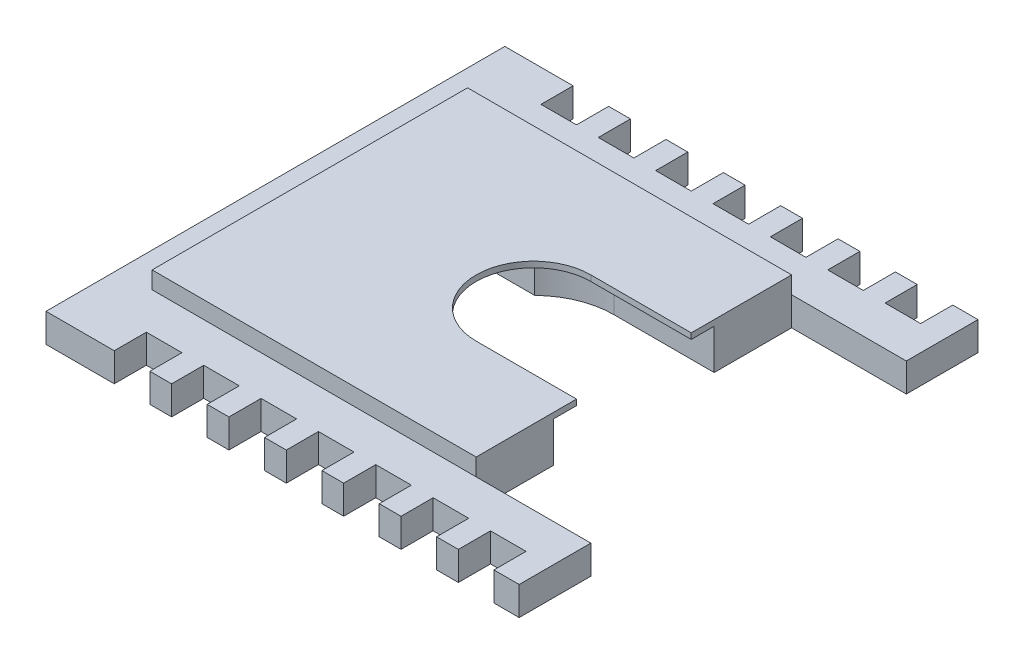
SolidWorks part; units mm, degrees
ref_plane "Front Plane" through (0, 0, 0) normal (0, 0, 1) x (1, 0, 0)
ref_plane "Top Plane" through (0, 0, 0) normal (0, 1, 0) x (1, 0, 0)
ref_plane "Right Plane" through (0, 0, 0) normal (1, 0, 0) x (0, 0, -1)
sketch "Sketch1" plane through (0, 0, 0) normal (0, 1, 0) x (1, 0, 0)
  line L0 (0, -50.8) -> (0, 50.8)
  line L16 (79.375, 34.925) -> (79.375, -34.925)
  line L17 (0, 0) -> (12.404, 0) construction
  line L18 (117.475, 34.925) -> (117.475, 0) construction
  line L19 (104.775, 50.8) -> (104.775, 34.925)
  line L20 (104.775, -34.925) -> (79.375, -34.925)
  line L21 (104.775, -50.8) -> (104.775, -34.925)
  line L22 (98.425, -50.8) -> (104.775, -50.8)
  line L23 (98.425, -44.45) -> (98.425, -50.8)
  line L24 (92.075, -44.45) -> (98.425, -44.45)
  line L25 (92.075, -50.8) -> (92.075, -44.45)
  line L26 (85.725, -50.8) -> (92.075, -50.8)
  line L27 (85.725, -44.45) -> (85.725, -50.8)
  line L29 (28.575, -50.8) -> (28.575, -44.45)
  line L30 (22.225, -50.8) -> (28.575, -50.8)
  line L31 (22.225, -44.45) -> (22.225, -50.8)
  line L32 (15.875, -44.45) -> (22.225, -44.45)
  line L33 (15.875, -50.8) -> (15.875, -44.45)
  line L34 (0, -50.8) -> (15.875, -50.8)
  line L35 (28.575, -44.45) -> (34.925, -44.45)
  line L36 (34.925, -44.45) -> (34.925, -50.8)
  line L37 (34.925, -50.8) -> (41.275, -50.8)
  line L38 (41.275, -50.8) -> (41.275, -44.45)
  line L39 (41.275, -44.45) -> (47.625, -44.45)
  line L40 (79.375, -44.45) -> (79.375, -50.8)
  line L41 (79.375, -50.8) -> (73.025, -50.8)
  line L42 (73.025, -50.8) -> (73.025, -44.45)
  line L43 (79.375, -44.45) -> (85.725, -44.45)
  line L44 (47.625, -44.45) -> (47.625, -50.8)
  line L45 (47.625, -50.8) -> (66.675, -50.8)
  line L46 (66.675, -50.8) -> (66.675, -44.45)
  line L47 (66.675, -44.45) -> (73.025, -44.45)
  line L48 (0, 50.8) -> (15.875, 50.8)
  line L49 (104.775, 34.925) -> (79.375, 34.925)
  line L50 (66.675, 44.45) -> (73.025, 44.45)
  line L51 (66.675, 50.8) -> (66.675, 44.45)
  line L52 (47.625, 50.8) -> (66.675, 50.8)
  line L53 (47.625, 44.45) -> (47.625, 50.8)
  line L54 (79.375, 44.45) -> (85.725, 44.45)
  line L55 (73.025, 50.8) -> (73.025, 44.45)
  line L56 (79.375, 50.8) -> (73.025, 50.8)
  line L57 (79.375, 44.45) -> (79.375, 50.8)
  line L58 (41.275, 44.45) -> (47.625, 44.45)
  line L59 (41.275, 50.8) -> (41.275, 44.45)
  line L60 (34.925, 50.8) -> (41.275, 50.8)
  line L61 (34.925, 44.45) -> (34.925, 50.8)
  line L62 (28.575, 44.45) -> (34.925, 44.45)
  line L63 (15.875, 50.8) -> (15.875, 44.45)
  line L64 (15.875, 44.45) -> (22.225, 44.45)
  line L65 (22.225, 44.45) -> (22.225, 50.8)
  line L66 (22.225, 50.8) -> (28.575, 50.8)
  line L67 (28.575, 50.8) -> (28.575, 44.45)
  line L68 (85.725, 44.45) -> (85.725, 50.8)
  line L69 (85.725, 50.8) -> (92.075, 50.8)
  line L70 (92.075, 50.8) -> (92.075, 44.45)
  line L71 (92.075, 44.45) -> (98.425, 44.45)
  line L72 (98.425, 44.45) -> (98.425, 50.8)
  line L73 (98.425, 50.8) -> (104.775, 50.8)
  circle A0 centre (57.15, 0) radius 12.7
  point P24 (79.375, 0)
  point P44 (57.15, -50.8)
  dimension "D7" = 25.4
  dimension "D1" = 44.45
  dimension "D2" = 6.35
  dimension "D3" = 69.85
  dimension "D4" = 101.6
  dimension "D5" = 25.4
  dimension "D6" = 15.875
extrude "Boss-Extrude1" add sketch "Sketch1" along normal blind 6.35
sketch "Sketch3" plane through (0, 6.35, 0) normal (0, 1, 0) x (1, 0, 0)
  line L1 (79.375, 34.925) -> (7.62, 34.925)
  line L2 (79.375, 34.925) -> (79.375, -34.925)
  line L3 (79.375, -34.925) -> (7.62, -34.925)
  line L4 (7.62, 34.925) -> (7.62, -34.925)
  line L5 (104.775, -34.925) -> (79.375, -34.925) construction
  line L6 (0, 50.8) -> (0, -50.8) construction
  circle A0 centre (57.15, 0) radius 17.78
  dimension "D2" = 35.56
  dimension "D1" = 7.62
extrude "Boss-Extrude2" add sketch "Sketch3" along normal blind 2.54
sketch "Sketch4" plane through (0, 0, 0) normal (0, -1, 0) x (1, 0, 0)
  circle A0 centre (57.15, 0) radius 17.78
  dimension "D1" = 35.56
extrude "Cut-Extrude1" cut sketch "Sketch4" against normal offset from surface (6.35 mm away) 2.54 up to face at (43.4975, 8.89, 0)
sketch "Sketch5" plane through (0, 0, 0) normal (0, -1, 0) x (-1, 0, 0)
  line L0 (-22.225, 44.45) -> (-15.875, 44.45) construction
  line L1 (-15.621, 51.054) -> (-22.479, 51.054)
  line L2 (-15.621, 51.054) -> (-15.621, 44.196)
  line L3 (-15.621, 44.196) -> (-22.479, 44.196)
  line L4 (-22.479, 51.054) -> (-22.479, 44.196)
  line L5 (-15.621, 51.054) -> (-22.479, 44.196) construction
  line L6 (-15.621, 44.196) -> (-22.479, 51.054) construction
  line L7 (-15.875, 44.45) -> (-15.875, 50.8) construction
  line L8 (-28.321, 51.054) -> (-35.179, 51.054)
  line L9 (-28.321, 51.054) -> (-28.321, 44.196)
  line L10 (-28.321, 44.196) -> (-35.179, 44.196)
  line L11 (-35.179, 51.054) -> (-35.179, 44.196)
  line L12 (-28.321, 51.054) -> (-35.179, 44.196) construction
  line L13 (-28.321, 44.196) -> (-35.179, 51.054) construction
  line L14 (-41.021, 51.054) -> (-47.879, 51.054)
  line L15 (-41.021, 51.054) -> (-41.021, 44.196)
  line L16 (-41.021, 44.196) -> (-47.879, 44.196)
  line L17 (-47.879, 51.054) -> (-47.879, 44.196)
  line L18 (-41.021, 51.054) -> (-47.879, 44.196) construction
  line L19 (-41.021, 44.196) -> (-47.879, 51.054) construction
  line L20 (-66.421, 51.054) -> (-73.279, 51.054)
  line L21 (-66.421, 51.054) -> (-66.421, 44.196)
  line L22 (-66.421, 44.196) -> (-73.279, 44.196)
  line L23 (-73.279, 51.054) -> (-73.279, 44.196)
  line L24 (-79.121, 51.054) -> (-85.979, 51.054)
  line L25 (-79.121, 51.054) -> (-79.121, 44.196)
  line L26 (-79.121, 44.196) -> (-85.979, 44.196)
  line L27 (-85.979, 51.054) -> (-85.979, 44.196)
  line L28 (-91.821, 51.054) -> (-98.679, 51.054)
  line L29 (-91.821, 51.054) -> (-91.821, 44.196)
  line L30 (-91.821, 44.196) -> (-98.679, 44.196)
  line L31 (-98.679, 51.054) -> (-98.679, 44.196)
  line L32 (-66.421, 51.054) -> (-73.279, 44.196) construction
  line L33 (-66.421, 44.196) -> (-73.279, 51.054) construction
  line L34 (-79.121, 51.054) -> (-85.979, 44.196) construction
  line L35 (-79.121, 44.196) -> (-85.979, 51.054) construction
  line L36 (-91.821, 51.054) -> (-98.679, 44.196) construction
  line L37 (-91.821, 44.196) -> (-98.679, 51.054) construction
  line L38 (0, 0) -> (-20.6098, 0) construction
  line L39 (-91.821, -44.196) -> (-98.679, -51.054) construction
  line L40 (-91.821, -51.054) -> (-98.679, -44.196) construction
  line L41 (-79.121, -44.196) -> (-85.979, -51.054) construction
  line L42 (-79.121, -51.054) -> (-85.979, -44.196) construction
  line L43 (-66.421, -44.196) -> (-73.279, -51.054) construction
  line L44 (-66.421, -51.054) -> (-73.279, -44.196) construction
  line L45 (-41.021, -44.196) -> (-47.879, -51.054) construction
  line L46 (-41.021, -51.054) -> (-47.879, -44.196) construction
  line L47 (-28.321, -44.196) -> (-35.179, -51.054) construction
  line L48 (-28.321, -51.054) -> (-35.179, -44.196) construction
  line L49 (-15.621, -44.196) -> (-22.479, -51.054) construction
  line L50 (-15.621, -51.054) -> (-22.479, -44.196) construction
  line L51 (-98.679, -51.054) -> (-98.679, -44.196)
  line L52 (-91.821, -44.196) -> (-98.679, -44.196)
  line L53 (-91.821, -51.054) -> (-91.821, -44.196)
  line L54 (-91.821, -51.054) -> (-98.679, -51.054)
  line L55 (-85.979, -51.054) -> (-85.979, -44.196)
  line L56 (-79.121, -44.196) -> (-85.979, -44.196)
  line L57 (-79.121, -51.054) -> (-79.121, -44.196)
  line L58 (-79.121, -51.054) -> (-85.979, -51.054)
  line L59 (-73.279, -51.054) -> (-73.279, -44.196)
  line L60 (-66.421, -44.196) -> (-73.279, -44.196)
  line L61 (-66.421, -51.054) -> (-66.421, -44.196)
  line L62 (-66.421, -51.054) -> (-73.279, -51.054)
  line L63 (-47.879, -51.054) -> (-47.879, -44.196)
  line L64 (-41.021, -44.196) -> (-47.879, -44.196)
  line L65 (-41.021, -51.054) -> (-41.021, -44.196)
  line L66 (-41.021, -51.054) -> (-47.879, -51.054)
  line L67 (-35.179, -51.054) -> (-35.179, -44.196)
  line L68 (-28.321, -44.196) -> (-35.179, -44.196)
  line L69 (-28.321, -51.054) -> (-28.321, -44.196)
  line L70 (-28.321, -51.054) -> (-35.179, -51.054)
  line L71 (-22.479, -51.054) -> (-22.479, -44.196)
  line L72 (-15.621, -44.196) -> (-22.479, -44.196)
  line L73 (-15.621, -51.054) -> (-15.621, -44.196)
  line L74 (-15.621, -51.054) -> (-22.479, -51.054)
  point P0 (-19.05, 47.625)
  point P7 (-19.05, 44.45)
  point P10 (-15.875, 47.625)
  point P12 (-31.75, 47.625)
  point P17 (-44.45, 47.625)
  point P22 (-69.85, 47.625)
  point P27 (-82.55, 47.625)
  point P32 (-95.25, 47.625)
  point P63 (-95.25, -47.625)
  point P64 (-82.55, -47.625)
  point P65 (-69.85, -47.625)
  point P66 (-44.45, -47.625)
  point P67 (-31.75, -47.625)
  point P68 (-19.05, -47.625)
  dimension "D1" = 6.858
  dimension "D2" = 3
  dimension "D3" = 2
extrude "Cut-Extrude2" cut sketch "Sketch5" against normal through all
sketch "Sketch7" plane through (0, 8.89, 0) normal (0, 1, 0) x (1, 0, 0)
  line L0 (79.375, -34.925) -> (79.375, 34.925) construction
  line L1 (7.62, 34.925) -> (79.375, 34.925)
  line L2 (7.62, 34.925) -> (7.62, -34.925)
  line L3 (7.62, -34.925) -> (79.375, -34.925)
  line L4 (79.375, 34.925) -> (79.375, -34.925)
  line L5 (7.62, -34.925) -> (79.375, -34.925) construction
  circle A0 centre (57.15, 0) radius 12.7
  dimension "D1" = 25.4
extrude "Boss-Extrude3" add sketch "Sketch7" along normal blind 1.27
sketch "Sketch8" plane through (0, 10.16, 0) normal (0, 1, 0) x (1, 0, 0)
  line L0 (57.15, 12.7) -> (79.375, 12.7)
  line L1 (79.375, -34.925) -> (79.375, 34.925) construction
  line L2 (79.375, 12.7) -> (79.375, -12.7)
  line L3 (79.375, -12.7) -> (57.15, -12.7)
  line L4 (57.15, -12.7) -> (57.15, 12.7)
  line L5 (47.879, -50.8) -> (66.421, -50.8) construction
  circle A0 centre (57.15, 0) radius 12.7 construction
  point P11 (57.15, -50.8)
extrude "Cut-Extrude4" cut sketch "Sketch8" against normal through all
sketch "Sketch9" plane through (0, 0, 0) normal (0, -1, 0) x (1, 0, 0)
  line L0 (57.15, 17.78) -> (57.15, 12.7)
  line L1 (25.4, -12.7) -> (57.15, -12.7)
  line L2 (25.4, -12.7) -> (25.4, 12.7)
  line L3 (25.4, 12.7) -> (57.15, 12.7)
  line L5 (47.879, 50.8) -> (66.421, 50.8) construction
  line L6 (57.15, 17.78) -> (79.375, 17.78)
  line L7 (79.375, 34.925) -> (79.375, 12.7) construction
  line L8 (57.15, -12.7) -> (57.15, -17.78)
  line L9 (57.15, -17.78) -> (79.375, -17.78)
  line L10 (79.375, -12.7) -> (79.375, -34.925) construction
  line L11 (79.375, -17.78) -> (79.375, 17.78)
  arc A0 (69.5934, 12.7) -> (69.5934, -12.7) centre (57.15, 0) ccw construction
  arc A1 (69.5934, 12.7) -> (69.5934, -12.7) centre (57.15, 0) ccw construction
  point P4 (25.4, 0)
  point P14 (57.15, 50.8)
  dimension "D1" = 25.4
  dimension "D3" = 25.4
extrude "Cut-Extrude5" cut sketch "Sketch9" against normal up to surface (8.89 mm away) up to face at (52.6409, 8.89, 0)
sketch "Sketch10" plane through (0, 0, 0) normal (0, 1, 0) x (1, 0, 0)
  line L0 (15.621, 50.8) -> (0, 50.8) construction
  line L1 (22.987, 50.8) -> (15.113, 50.8)
  line L2 (22.987, 50.8) -> (22.987, 43.688)
  line L3 (22.987, 43.688) -> (15.113, 43.688)
  line L4 (15.113, 50.8) -> (15.113, 43.688)
  line L5 (22.987, 50.8) -> (15.113, 43.688) construction
  line L6 (22.987, 43.688) -> (15.113, 50.8) construction
  line L7 (22.479, 44.196) -> (15.621, 44.196) construction
  line L8 (19.05, 44.196) -> (19.05, 43.688) construction
  line L9 (15.621, 44.196) -> (15.113, 44.196) construction
  line L11 (35.687, 50.8) -> (27.813, 50.8)
  line L12 (35.687, 50.8) -> (35.687, 43.688)
  line L13 (35.687, 43.688) -> (27.813, 43.688)
  line L14 (27.813, 50.8) -> (27.813, 43.688)
  line L15 (35.687, 50.8) -> (27.813, 43.688) construction
  line L16 (35.687, 43.688) -> (27.813, 50.8) construction
  line L17 (31.75, 44.196) -> (31.75, 43.688) construction
  line L18 (28.321, 44.196) -> (27.813, 44.196) construction
  line L19 (48.387, 50.8) -> (40.513, 50.8)
  line L20 (48.387, 50.8) -> (48.387, 43.688)
  line L21 (48.387, 43.688) -> (40.513, 43.688)
  line L22 (40.513, 50.8) -> (40.513, 43.688)
  line L23 (48.387, 50.8) -> (40.513, 43.688) construction
  line L24 (48.387, 43.688) -> (40.513, 50.8) construction
  line L25 (44.45, 44.196) -> (44.45, 43.688) construction
  line L26 (41.021, 44.196) -> (40.513, 44.196) construction
  line L27 (61.087, 50.8) -> (53.213, 50.8)
  line L28 (61.087, 50.8) -> (61.087, 43.688)
  line L29 (61.087, 43.688) -> (53.213, 43.688)
  line L30 (53.213, 50.8) -> (53.213, 43.688)
  line L31 (61.087, 50.8) -> (53.213, 43.688) construction
  line L32 (61.087, 43.688) -> (53.213, 50.8) construction
  line L33 (57.15, 44.196) -> (57.15, 43.688) construction
  line L34 (53.721, 44.196) -> (53.213, 44.196) construction
  line L35 (73.787, 50.8) -> (65.913, 50.8)
  line L36 (73.787, 50.8) -> (73.787, 43.688)
  line L37 (73.787, 43.688) -> (65.913, 43.688)
  line L38 (65.913, 50.8) -> (65.913, 43.688)
  line L39 (73.787, 50.8) -> (65.913, 43.688) construction
  line L40 (73.787, 43.688) -> (65.913, 50.8) construction
  line L41 (69.85, 44.196) -> (69.85, 43.688) construction
  line L42 (66.421, 44.196) -> (65.913, 44.196) construction
  line L43 (86.487, 50.8) -> (78.613, 50.8)
  line L44 (86.487, 50.8) -> (86.487, 43.688)
  line L45 (86.487, 43.688) -> (78.613, 43.688)
  line L46 (78.613, 50.8) -> (78.613, 43.688)
  line L47 (86.487, 50.8) -> (78.613, 43.688) construction
  line L48 (86.487, 43.688) -> (78.613, 50.8) construction
  line L49 (82.55, 44.196) -> (82.55, 43.688) construction
  line L50 (79.121, 44.196) -> (78.613, 44.196) construction
  line L51 (99.187, 50.8) -> (91.313, 50.8)
  line L52 (99.187, 50.8) -> (99.187, 43.688)
  line L53 (99.187, 43.688) -> (91.313, 43.688)
  line L54 (91.313, 50.8) -> (91.313, 43.688)
  line L55 (99.187, 50.8) -> (91.313, 43.688) construction
  line L56 (99.187, 43.688) -> (91.313, 50.8) construction
  line L57 (95.25, 44.196) -> (95.25, 43.688) construction
  line L58 (91.821, 44.196) -> (91.313, 44.196) construction
  line L59 (35.687, -43.688) -> (27.813, -43.688)
  line L60 (35.687, -43.688) -> (35.687, -50.8)
  line L61 (35.687, -50.8) -> (27.813, -50.8)
  line L62 (27.813, -43.688) -> (27.813, -50.8)
  line L63 (35.687, -43.688) -> (27.813, -50.8) construction
  line L64 (35.687, -50.8) -> (27.813, -43.688) construction
  line L65 (31.75, -50.292) -> (31.75, -50.8) construction
  line L66 (28.321, -50.292) -> (27.813, -50.292) construction
  line L67 (48.387, -43.688) -> (40.513, -43.688)
  line L68 (48.387, -43.688) -> (48.387, -50.8)
  line L69 (48.387, -50.8) -> (40.513, -50.8)
  line L70 (40.513, -43.688) -> (40.513, -50.8)
  line L71 (48.387, -43.688) -> (40.513, -50.8) construction
  line L72 (48.387, -50.8) -> (40.513, -43.688) construction
  line L73 (44.45, -50.292) -> (44.45, -50.8) construction
  line L74 (41.021, -50.292) -> (40.513, -50.292) construction
  line L75 (61.087, -43.688) -> (53.213, -43.688)
  line L76 (61.087, -43.688) -> (61.087, -50.8)
  line L77 (61.087, -50.8) -> (53.213, -50.8)
  line L78 (53.213, -43.688) -> (53.213, -50.8)
  line L79 (61.087, -43.688) -> (53.213, -50.8) construction
  line L80 (61.087, -50.8) -> (53.213, -43.688) construction
  line L81 (57.15, -50.292) -> (57.15, -50.8) construction
  line L82 (53.721, -50.292) -> (53.213, -50.292) construction
  line L83 (73.787, -43.688) -> (65.913, -43.688)
  line L84 (73.787, -43.688) -> (73.787, -50.8)
  line L85 (73.787, -50.8) -> (65.913, -50.8)
  line L86 (65.913, -43.688) -> (65.913, -50.8)
  line L87 (73.787, -43.688) -> (65.913, -50.8) construction
  line L88 (73.787, -50.8) -> (65.913, -43.688) construction
  line L89 (69.85, -50.292) -> (69.85, -50.8) construction
  line L90 (66.421, -50.292) -> (65.913, -50.292) construction
  line L91 (86.487, -43.688) -> (78.613, -43.688)
  line L92 (86.487, -43.688) -> (86.487, -50.8)
  line L93 (86.487, -50.8) -> (78.613, -50.8)
  line L94 (78.613, -43.688) -> (78.613, -50.8)
  line L95 (86.487, -43.688) -> (78.613, -50.8) construction
  line L96 (86.487, -50.8) -> (78.613, -43.688) construction
  line L97 (82.55, -50.292) -> (82.55, -50.8) construction
  line L98 (79.121, -50.292) -> (78.613, -50.292) construction
  line L99 (99.187, -43.688) -> (91.313, -43.688)
  line L100 (99.187, -43.688) -> (99.187, -50.8)
  line L101 (99.187, -50.8) -> (91.313, -50.8)
  line L102 (91.313, -43.688) -> (91.313, -50.8)
  line L103 (99.187, -43.688) -> (91.313, -50.8) construction
  line L104 (99.187, -50.8) -> (91.313, -43.688) construction
  line L105 (95.25, -50.292) -> (95.25, -50.8) construction
  line L106 (91.821, -50.292) -> (91.313, -50.292) construction
  line L107 (22.987, -43.688) -> (15.113, -43.688)
  line L108 (22.987, -43.688) -> (22.987, -50.8)
  line L109 (22.987, -50.8) -> (15.113, -50.8)
  line L110 (15.113, -43.688) -> (15.113, -50.8)
  line L111 (22.987, -43.688) -> (15.113, -50.8) construction
  line L112 (22.987, -50.8) -> (15.113, -43.688) construction
  line L113 (19.05, -50.292) -> (19.05, -50.8) construction
  line L114 (15.621, -50.292) -> (15.113, -50.292) construction
  line L115 (0, -50.8) -> (15.621, -50.8) construction
  point P0 (19.05, 47.244)
  point P15 (31.75, 47.244)
  point P25 (44.45, 47.244)
  point P34 (57.15, 47.244)
  point P43 (69.85, 47.244)
  point P52 (82.55, 47.244)
  point P61 (95.25, 47.244)
  point P70 (31.75, -47.244)
  point P79 (44.45, -47.244)
  point P88 (57.15, -47.244)
  point P97 (69.85, -47.244)
  point P106 (82.55, -47.244)
  point P115 (95.25, -47.244)
  point P124 (19.05, -47.244)
  dimension "D1" = 0.508
  dimension "D2" = 7
  dimension "D3" = 2
extrude "Cut-Extrude7" cut sketch "Sketch10" against normal through all and the other way through all
